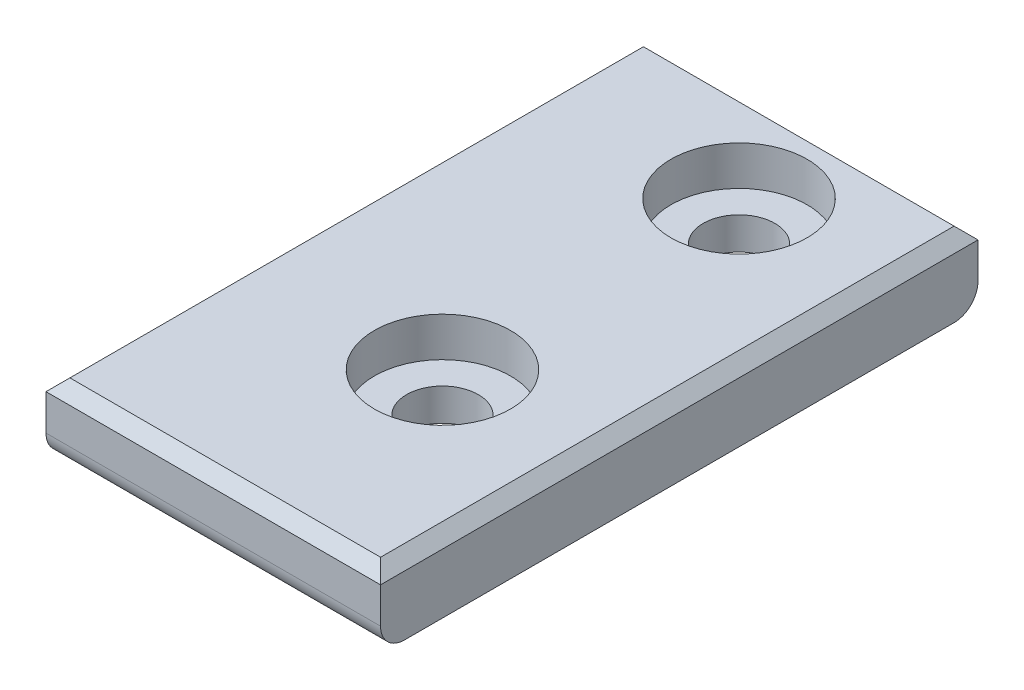
SolidWorks part; units mm, degrees
ref_plane "Front Plane" through (0, 0, 0) normal (0, 0, 1) x (1, 0, 0)
ref_plane "Top Plane" through (0, 0, 0) normal (0, 1, 0) x (1, 0, 0)
ref_plane "Right Plane" through (0, 0, 0) normal (1, 0, 0) x (0, 0, -1)
sketch "Sketch1" plane through (0, 0, 0) normal (0, 1, 0) x (1, 0, 0)
  line L1 (0, 0) -> (14, 0)
  line L2 (0, 0) -> (0, 25)
  line L3 (0, 25) -> (14, 25)
  line L4 (14, 0) -> (14, 25)
  circle A0 centre (8, 21) radius 1.5
  circle A1 centre (8, 8.5895) radius 1.5
  dimension "D6" = 3
  dimension "D1" = 14
  dimension "D2" = 25
  dimension "D3" = 4
  dimension "D4" = 6
  dimension "D5" = 16.4105
extrude "Boss-Extrude1" add sketch "Sketch1" along normal blind 3
chamfer "Chamfer1" distance 0.5 angle 45 4 edges at (7, 3, -25) (0, 3, -12.5) (7, 3, 0) (14, 3, -12.5)
fillet "Fillet1" radius 1 2 edges at (7, 0, 0) (7, 0, -25)
sketch "Sketch2" plane through (0, 3, 0) normal (0, 1, 0) x (1, 0, 0)
  circle A0 centre (8, 21) radius 2.85
  circle A1 centre (8, 8.5895) radius 2.85
  dimension "D1" = 5.7
extrude "Cut-Extrude1" cut sketch "Sketch2" against normal blind 1.65
sketch "Sketch3" plane through (0, 0, 0) normal (0, -1, 0) x (1, 0, 0)
  line L0 (14, -25) -> (0, -25) construction
  line L1 (5.5, -25) -> (10.5, -25)
  line L2 (4.5, -24) -> (4.5, -23)
  line L3 (4.5, -23) -> (11.5, -23)
  line L4 (11.5, -24) -> (11.5, -23)
  line L6 (14, -25) -> (14, -24) construction
  arc A0 (4.5, -24) -> (5.5, -25) centre (5.5, -24) ccw
  arc A1 (10.5, -25) -> (11.5, -24) centre (10.5, -24) ccw
  point P11 (4.5, -25)
  point P14 (11.5, -25)
  dimension "D4" = 1
  dimension "D1" = 2.5
  dimension "D2" = 7
  dimension "D3" = 2
extrude "Boss-Extrude2" add sketch "Sketch3" against normal up to vertex (1 mm away) up to point (0, 1, -25)
